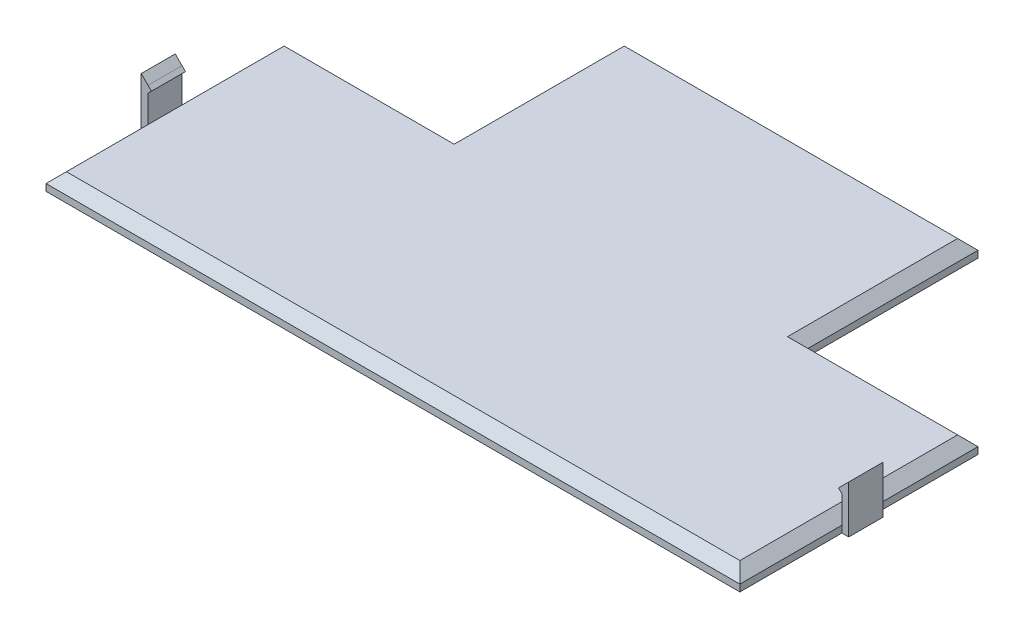
SolidWorks part; units mm, degrees
ref_plane "Front Plane" through (0, 0, 0) normal (0, 0, 1) x (1, 0, 0)
ref_plane "Top Plane" through (0, 0, 0) normal (0, 1, 0) x (1, 0, 0)
ref_plane "Right Plane" through (0, 0, 0) normal (1, 0, 0) x (0, 0, -1)
sketch "Sketch1" plane through (0, 0, 0) normal (0, 1, 0) x (1, 0, 0)
  line L0 (-96.8056, 26.5278) -> (-46.8056, 26.5278)
  line L1 (-46.8056, 26.5278) -> (-46.8056, 76.5278)
  line L2 (-46.8056, 76.5278) -> (57.1944, 76.5278)
  line L3 (57.1944, 76.5278) -> (57.1944, 26.5278)
  line L4 (57.1944, 26.5278) -> (107.1944, 26.5278)
  line L6 (107.1944, -43.4722) -> (-96.8056, -43.4722)
  line L7 (-96.8056, -43.4722) -> (-96.8056, 26.5278)
  line L8 (107.1944, 26.5278) -> (107.1944, -43.4722)
  dimension "D1" = 50
  dimension "D2" = 104
  dimension "D3" = 50
  dimension "D4" = 50
  dimension "D5" = 50
  dimension "D6" = 70
extrude "Boss-Extrude1" add sketch "Sketch1" along normal blind 5
chamfer "Chamfer1" distance 3 angle 45 8 edges at (5.1944, 5, 43.4722) (-96.8056, 5, 8.4722) (-71.8056, 5, -26.5278) (-46.8056, 5, -51.5278) (5.1944, 5, -76.5278) (57.1944, 5, -51.5278) (82.1944, 5, -26.5278) (107.1944, 5, 8.4722)
ref_plane "Plane1" through (-46.8056, 0, -76.5278) normal (0, -1, 0) x (-1, 0, 0)
sketch "Sketch4" plane through (107.1944, 0, 0) normal (1, 0, 0) x (0, 0, -1)
  line L0 (26.5278, 2) -> (-43.4722, 2) construction
  line L1 (-13.4722, 2) -> (-3.4722, 2)
  line L2 (-13.4722, 2) -> (-13.4722, 0)
  line L3 (-13.4722, 0) -> (-3.4722, 0)
  line L4 (-3.4722, 2) -> (-3.4722, 0)
  line L5 (-43.4722, 0) -> (26.5278, 0) construction
  line L6 (-43.4722, 2) -> (-43.4722, 0) construction
  line L7 (26.5278, 2) -> (26.5278, 0) construction
  point P12 (26.5278, 1)
  dimension "D1" = 30
  dimension "D2" = 30
extrude "Boss-Extrude3" add sketch "Sketch4" along normal blind 2
sketch "Sketch5" plane through (0, 2, 0) normal (0, 1, 0) x (1, 0, 0)
  line L1 (107.1944, -3.4722) -> (109.1944, -3.4722)
  line L2 (107.1944, -3.4722) -> (107.1944, -13.4722)
  line L3 (107.1944, -13.4722) -> (109.1944, -13.4722)
  line L4 (109.1944, -3.4722) -> (109.1944, -13.4722)
extrude "Boss-Extrude4" add sketch "Sketch5" along normal blind 12
chamfer "Chamfer2" distance 2 angle 45 1 edges at (107.1944, 14, 8.4722)
sketch "Sketch6" plane through (107.1944, 0, 0) normal (-1, 0, 0) x (0, 0, 1)
  line L0 (13.4722, 12) -> (13.4722, 2) construction
  line L1 (3.4722, 12) -> (13.4722, 12)
  line L2 (3.4722, 12) -> (3.4722, 10)
  line L3 (3.4722, 10) -> (13.4722, 10)
  line L4 (13.4722, 12) -> (13.4722, 10)
  dimension "D1" = 2
extrude "Boss-Extrude5" add sketch "Sketch6" along normal blind 1
chamfer "Chamfer3" distance 1 angle 45 2 edges at (106.1944, 10, 8.4722) (106.1944, 12, 8.4722)
sketch "Sketch7" plane through (-96.8056, 0, 0) normal (-1, 0, 0) x (0, 0, 1)
  line L0 (43.4722, 2) -> (-26.5278, 2) construction
  line L1 (3.4722, 2) -> (13.4722, 2)
  line L2 (3.4722, 2) -> (3.4722, 0)
  line L3 (3.4722, 0) -> (13.4722, 0)
  line L4 (13.4722, 2) -> (13.4722, 0)
  line L5 (3.4722, 10) -> (3.4722, 2) construction
  line L6 (-26.5278, 0) -> (43.4722, 0) construction
  line L8 (43.4722, 2) -> (43.4722, 0) construction
  dimension "D1" = 30
extrude "Boss-Extrude6" add sketch "Sketch7" along normal blind 2
sketch "Sketch8" plane through (0, 2, 0) normal (0, 1, 0) x (1, 0, 0)
  line L1 (-98.8056, -3.4722) -> (-96.8056, -3.4722)
  line L2 (-98.8056, -3.4722) -> (-98.8056, -13.4722)
  line L3 (-98.8056, -13.4722) -> (-96.8056, -13.4722)
  line L4 (-96.8056, -3.4722) -> (-96.8056, -13.4722)
extrude "Boss-Extrude7" add sketch "Sketch8" along normal blind 12
chamfer "Chamfer4" distance 2 angle 45 1 edges at (-96.8056, 14, 8.4722)
sketch "Sketch9" plane through (-96.8056, 0, 0) normal (1, 0, 0) x (0, 0, -1)
  line L0 (-3.4722, 12) -> (-3.4722, 2) construction
  line L1 (-13.4722, 12) -> (-3.4722, 12)
  line L2 (-13.4722, 12) -> (-13.4722, 10)
  line L3 (-13.4722, 10) -> (-3.4722, 10)
  line L4 (-3.4722, 12) -> (-3.4722, 10)
  dimension "D1" = 2
extrude "Boss-Extrude8" add sketch "Sketch9" along normal blind 1
chamfer "Chamfer5" distance 1 angle 45 2 edges at (-95.8056, 10, 8.4722) (-95.8056, 12, 8.4722)
